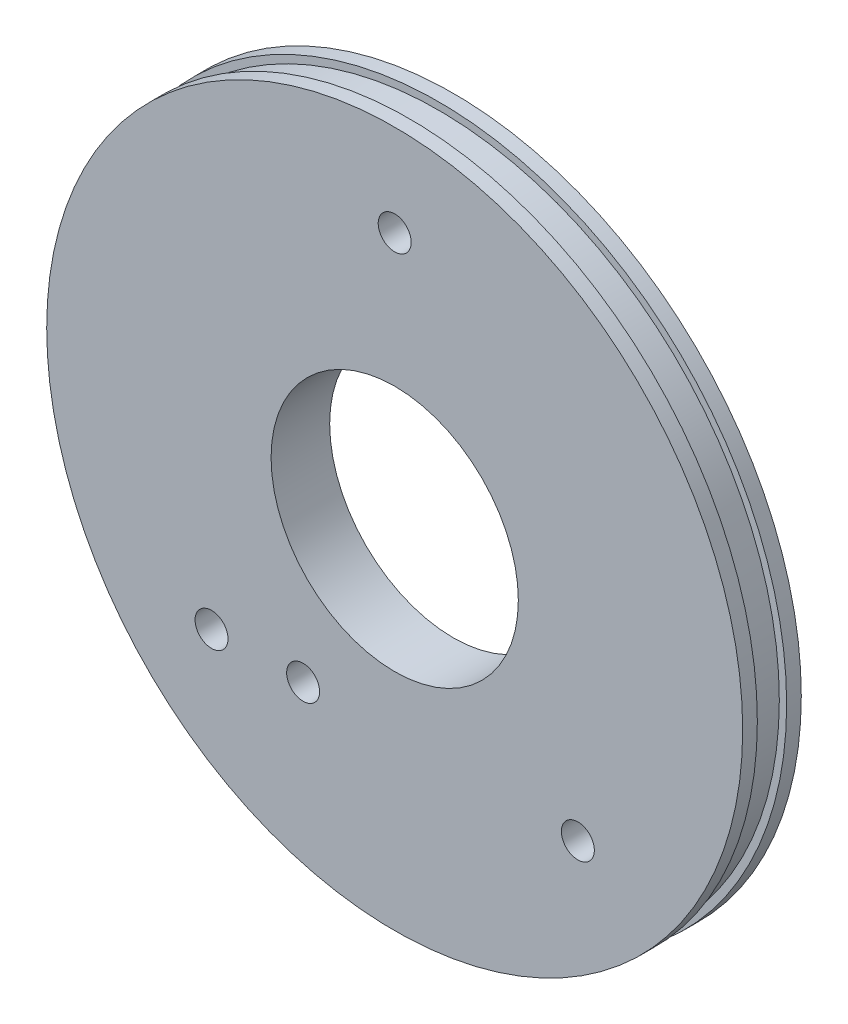
SolidWorks part; units mm, degrees
ref_plane "Front Plane" through (0, 0, 0) normal (0, 0, 1) x (1, 0, 0)
ref_plane "Top Plane" through (0, 0, 0) normal (0, 1, 0) x (1, 0, 0)
ref_plane "Right Plane" through (0, 0, 0) normal (1, 0, 0) x (0, 0, -1)
sketch "Sketch2" plane through (0, 0, 0) normal (0, 0, 1) x (1, 0, 0)
  circle A0 centre (0, 0) radius 93
  circle A1 centre (0, 0) radius 95
  dimension "D1" = 186
  dimension "D2" = 190
extrude "Boss-Extrude1" add sketch "Sketch2" along normal blind 8 and the other way blind 8 contours A1 A0 | A0 region at (-94.7313, 0, 0)
extrude "Cut-Extrude1" cut sketch "Sketch2<5>" against normal blind 4 and the other way blind 4
sketch "Sketch2<5>" plane through (0, 0, 0) normal (0, 0, 1) x (1, 0, 0) same geometry as "Sketch2"
sketch "Sketch3" plane through (0, 0, 8) normal (0, 0, 1) x (1, 0, 0)
  line L0 (0, 33.75) -> (0, -33.75) construction
  line L1 (41.5, 33.75) -> (-78.5, 33.75)
  line L2 (41.5, 33.75) -> (41.5, -33.75)
  line L3 (41.5, -33.75) -> (-78.5, -33.75) construction
  line L4 (-78.5, 33.75) -> (-78.5, -33.75) construction
  line L5 (31, 33.75) -> (31, -33.75) construction
  line L6 (41.5, 0) -> (-78.5, 0) construction
  line L7 (-78.5, 28.75) -> (-43.5, 28.75)
  line L8 (-43.5, 28.75) -> (-43.5, -33.75)
  line L9 (-78.5, 33.75) -> (-78.5, 28.75)
  line L10 (-43.5, -33.75) -> (41.5, -33.75)
  circle A0 centre (0, 0) radius 31
  circle A1 centre (0, 0) radius 33.75
  point P9 (0, 0)
  dimension "D3" = 62
  dimension "D7" = 67.5
  dimension "D1" = 10.5
  dimension "D2" = 120
  dimension "D4" = 67.5
  dimension "D5" = 5
  dimension "D6" = 35
sketch "Sketch4" plane through (0, 0, -8) normal (0, 0, 1) x (1, 0, 0)
  line L0 (0, 33.75) -> (0, -33.75) construction
  line L1 (41.5, 33.75) -> (-78.5, 33.75)
  line L2 (41.5, 33.75) -> (41.5, -33.75)
  line L3 (41.5, -33.75) -> (-78.5, -33.75) construction
  line L4 (-78.5, 33.75) -> (-78.5, -33.75) construction
  line L5 (31, 33.75) -> (31, -33.75) construction
  line L6 (41.5, 0) -> (-78.5, 0) construction
  line L7 (-78.5, 28.75) -> (-43.5, 28.75)
  line L8 (-43.5, 28.75) -> (-43.5, -33.75)
  line L9 (-78.5, 33.75) -> (-78.5, 28.75)
  line L10 (-43.5, -33.75) -> (41.5, -33.75)
  circle A0 centre (0, 0) radius 31
  point P9 (0, 0)
  dimension "D3" = 62
  dimension "D1" = 10.5
  dimension "D2" = 120
  dimension "D4" = 67.5
  dimension "D5" = 5
  dimension "D6" = 35
ref_plane "Plane1" through (0, -33.75, 0) normal (0, 1, 0) x (1, 0, 0)
sketch "Sketch7" plane through (0, 0, 8) normal (0, 0, 1) x (1, 0, 0)
  line L0 (0, -33.75) -> (0, -48.75) construction
  line L1 (-50, -48.75) -> (50, -48.75) construction
  line L2 (0, -48.75) -> (20, -48.75) construction
  line L3 (0, -48.75) -> (-6.4741, -48.75) construction
  circle A0 centre (-50, -48.75) radius 4.5
  circle A1 centre (50, -48.75) radius 4.5
  circle A5 centre (-25, -48.75) radius 4.5
  point P7 (0, -48.75)
  dimension "D3" = 9
  dimension "D4" = 9
  dimension "D5" = 9
  dimension "D1" = 100
  dimension "D2" = 15
  dimension "D6" = 25
extrude "Cut-Extrude2" cut sketch "Sketch7" against normal blind 167
extrude "Cut-Extrude3" cut sketch "Sketch3" against normal blind 43 contours L1 A1 L10 A0 | A0 | A1 region at (23.1899, 23.1899, 8) region at (0, 0, 8)
sketch "Sketch10" plane through (0, 0, -8) normal (0, 0, -1) x (-1, 0, 0)
  line L0 (0, 0) -> (0, 70) construction
  circle A0 centre (0, 70) radius 4.5
  circle A1 centre (0, 70) radius 6
  dimension "D2" = 9
  dimension "D3" = 12
  dimension "D1" = 70
extrude "Cut-Extrude4" cut sketch "Sketch10" against normal blind 60 and the other way blind 112 contours A0 region at (0, 70, -8)
